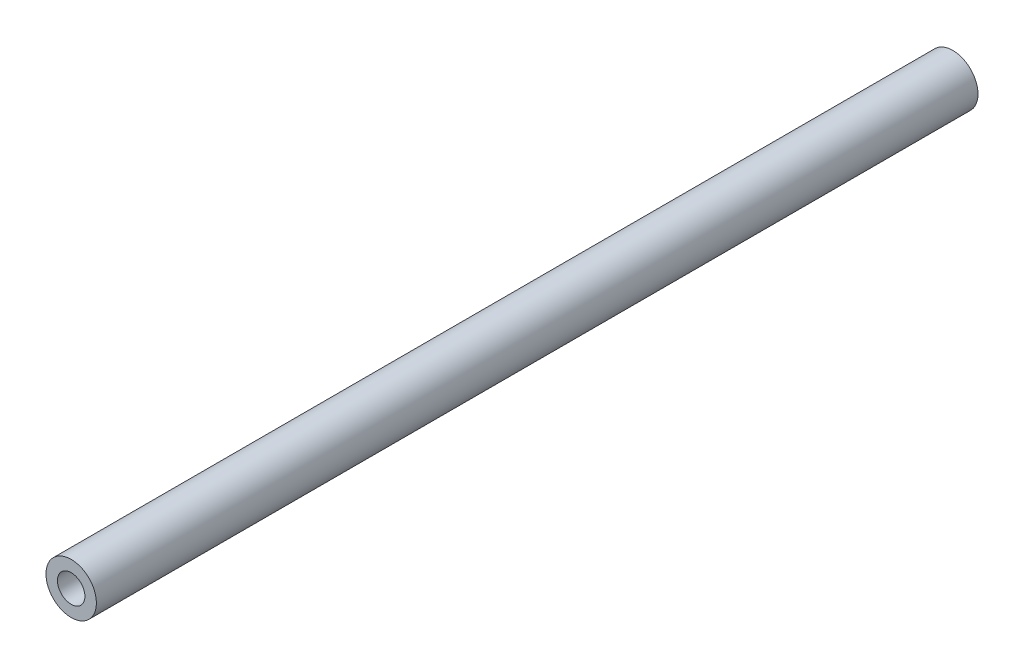
SolidWorks part; units mm, degrees
material "AISI 4130 Steel, normalized at 870C"
ref_plane "Front Plane" through (0, 0, 0) normal (0, 0, 1) x (1, 0, 0)
ref_plane "Top Plane" through (0, 0, 0) normal (0, 1, 0) x (1, 0, 0)
ref_plane "Right Plane" through (0, 0, 0) normal (1, 0, 0) x (0, 0, -1)
sketch "Sketch1" plane through (0, 0, 0) normal (0, 0, 1) x (1, 0, 0)
  circle A0 centre (0, 0) radius 6.35
  dimension "D1" = 12.7
extrude "Boss-ExtrudeShaft" add sketch "Sketch1" along normal blind 111 and the other way blind 111
sketch3d "3DSketch1"
  line L0 (0, 0, 111) -> (0, 0, 0) construction
  line L1 (0, 0, -111) -> (0, 0, 111) construction
  line L2 (0, 0, 0) -> (0, 10.0458, 0) construction
  line L3 (0, 0, 0) -> (9.7075, 0, 0) construction
sketch "Sketch2" plane through (0, 0, 111) normal (0, 0, 1) x (1, 0, 0)
  circle A0 centre (0, 0) radius 3.455
  dimension "D1" = 6.91
sketch "Sketch3" plane through (0, 0, -111) normal (0, 0, -1) x (-1, 0, 0)
  circle A0 centre (0, 0) radius 3.455
  dimension "D1" = 6.91
hole_wizard "5/16-24 Tapped Hole2" positions "3DSketch4" profile "Sketch6" tap size "5/16-24" standard "ANSI Inch"
sketch3d "3DSketch4"
  point P0 (0, 0, -111)
  point P3 (0, 0, 111)
sketch "Sketch6" plane through (0, 0, -111) normal (1, 0, 0) x (0, 1, 0)
  line L0 (0, 0) -> (0, 42.0756)
  line L1 (0, 42.0756) -> (3.4544, 40)
  line L2 (3.4544, 40) -> (3.4544, 0)
  line L5 (3.4544, 0) -> (0, 0)
  line L10 (0, 42.0756) -> (-3.4544, 40) construction
  line L11 (0, -6.35) -> (0, 107.95) construction
  dimension "Tap Drill Dia." = 6.9088
  dimension "Tap Drill Depth" = 40
  dimension "Drill Angle" = 118
cosmetic thread "Hole Thread4"
cosmetic thread "Hole Thread5"
